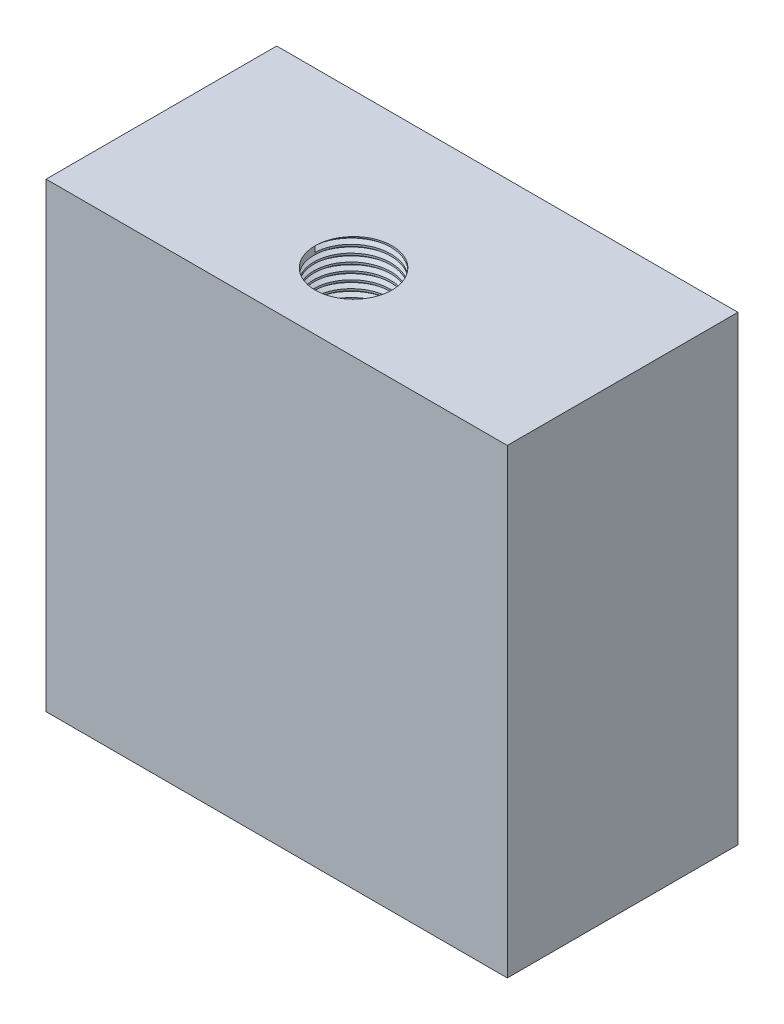
SolidWorks part; units mm, degrees
ref_plane "Front Plane" through (0, 0, 0) normal (0, 0, 1) x (1, 0, 0)
ref_plane "Top Plane" through (0, 0, 0) normal (0, 1, 0) x (1, 0, 0)
ref_plane "Right Plane" through (0, 0, 0) normal (1, 0, 0) x (0, 0, -1)
sketch "Sketch2" plane through (0, 0, 0) normal (0, 0, 1) x (1, 0, 0)
  line L1 (-38.1, -38.1) -> (38.1, -38.1)
  line L2 (-38.1, -38.1) -> (-38.1, 38.1)
  line L3 (-38.1, 38.1) -> (38.1, 38.1)
  line L4 (38.1, -38.1) -> (38.1, 38.1)
  line L5 (-38.1, -38.1) -> (38.1, 38.1) construction
  line L6 (-38.1, 38.1) -> (38.1, -38.1) construction
  point P0 (0, 0)
  dimension "D1" = 76.2
  dimension "D2" = 76.2
extrude "Boss-Extrude1" add sketch "Sketch2" along normal blind 38.1
sketch "Sketch3" plane through (0, 0, 0) normal (0, 0, -1) x (-1, 0, 0)
  circle A0 centre (0, 0) radius 25.4
  dimension "D1" = 50.8
extrude "Cut-Extrude1" cut sketch "Sketch3" against normal blind 12.7
sketch "Sketch5" plane through (0, 38.1, 0) normal (0, 1, 0) x (1, 0, 0)
  line L0 (38.1, 0) -> (-38.1, 0) construction
  circle A0 centre (0, -25.4) radius 6.35
  point P4 (0, 0)
  dimension "D1" = 12.7
  dimension "D2" = 25.4
extrude "Cut-Extrude3" cut sketch "Sketch5" against normal blind 25.4
thread "Thread1" pitch 1.27 method cut profile "Thread Profile2" start angle 0, offset 0, length 12.7, pitch 1.27, diameter 12.7
ref_plane "Plane2" through (-6.35, 38.1, 25.4) normal (0, 0, 1) x (-1, 0, 0)
sketch "Thread Profile2" plane through (-6.35, 38.1, 25.4) normal (0, 0, 1) x (-1, 0, 0)
  line L0 (0, 0) -> (0, 1.27) construction
  line L1 (0, 0) -> (0.6874, 0.3969)
  line L2 (0.6874, 0.3969) -> (0.6874, 0.5556)
  line L3 (0.6874, 0.5556) -> (0, 0.9525)
  line L4 (0.6874, 0.4762) -> (0, 0.4762) construction
  line L11 (0, 0) -> (0, 0.9525)
  point P2 (0, 0)
  dimension "Pitch" = 1.27
  dimension "Profile_Angle" = 60
  dimension "Profile_Land" = 0.1588
  dimension "Profile_Height" = 0.6874
sketch "Sketch19" plane through (0, 0, 12.7) normal (0, 0, -1) x (-1, 0, 0)
  circle A0 centre (0, 15.24) radius 3.175
  dimension "D1" = 6.35
extrude "Cut-Extrude7" cut sketch "Sketch19" against normal blind 12.7
thread "Thread2" pitch 3.175 method cut profile "Thread Profile3" start angle 0, offset 0, length 12.7, pitch 3.175, diameter 50.8
ref_plane "Plane3" through (25.4, 0, 0) normal (0, -1, 0) x (1, 0, 0)
sketch "Thread Profile3" plane through (25.4, 0, 0) normal (0, -1, 0) x (1, 0, 0)
  line L0 (0, 0) -> (0, 3.175) construction
  line L1 (0, 0) -> (1.7185, 0.9922)
  line L2 (1.7185, 0.9922) -> (1.7185, 1.3891)
  line L3 (1.7185, 1.3891) -> (0, 2.3812)
  line L4 (1.7185, 1.1906) -> (0, 1.1906) construction
  line L11 (0, 0) -> (0, 2.3812)
  point P2 (0, 0)
  dimension "Pitch" = 3.175
  dimension "Profile_Angle" = 60
  dimension "Profile_Land" = 0.3969
  dimension "Profile_Height" = 1.7185
